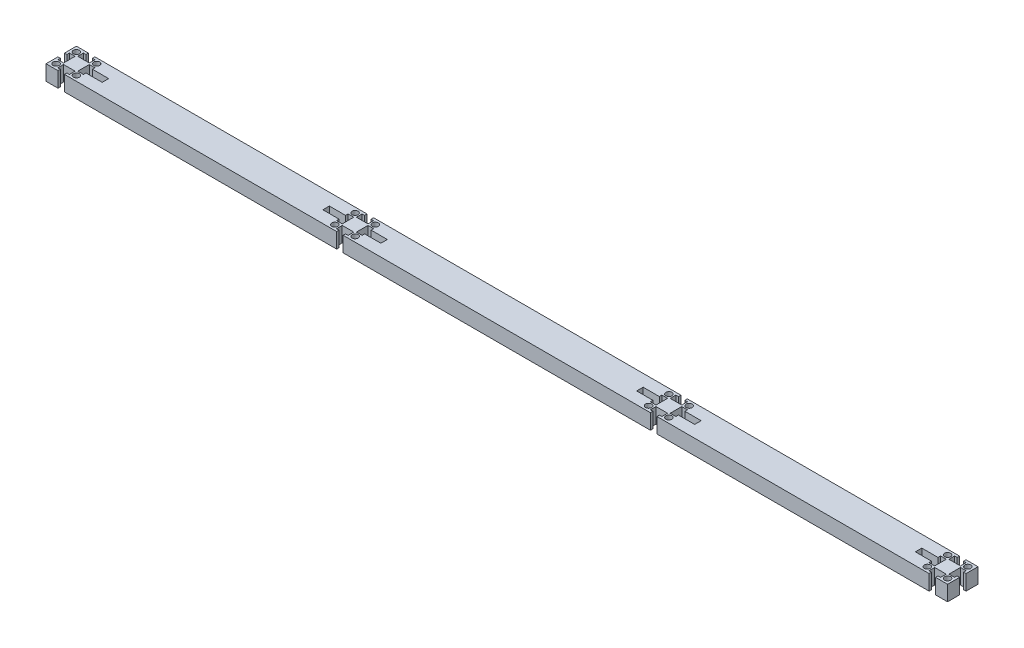
SolidWorks part; units mm, degrees
ref_plane "Front Plane" through (0, 0, 0) normal (0, 0, 1) x (1, 0, 0)
ref_plane "Top Plane" through (0, 0, 0) normal (0, 1, 0) x (1, 0, 0)
ref_plane "Right Plane" through (0, 0, 0) normal (1, 0, 0) x (0, 0, -1)
sketch "Sketch1" plane through (0, 0, 0) normal (0, 1, 0) x (1, 0, 0)
  line L1 (0, 0) -> (152.4, 0)
  line L2 (0, 0) -> (0, 15)
  line L3 (0, 15) -> (152.4, 15)
  line L6 (21.8, 9.1) -> (21.8, 5.9)
  line L7 (5.9, 0) -> (9.1, 0)
  line L8 (0, 5.9) -> (0, 9.1)
  line L9 (4, 4.65) -> (4, 7.5)
  line L10 (4, 7.5) -> (4, 10.35)
  line L11 (4, 10.35) -> (1.2, 10.35)
  line L12 (76.2, 0) -> (76.2, 15)
  line L14 (152.4, 0) -> (292.1, 0)
  line L15 (152.4, 15) -> (292.1, 15)
  line L16 (222.25, 0) -> (222.25, 15)
  line L18 (444.5, 15) -> (292.1, 15)
  line L20 (444.5, 0) -> (292.1, 0)
  line L21 (444.5, 0) -> (444.5, 15)
  line L22 (1.2, 10.35) -> (1.2, 9.1)
  line L23 (1.2, 9.1) -> (0, 9.1)
  line L24 (7.5, 4) -> (4.65, 4)
  line L25 (4.65, 4) -> (4.65, 1.2)
  line L27 (10.35, 1.2) -> (10.35, 4)
  line L28 (10.35, 4) -> (7.5, 4)
  line L29 (4.65, 1.2) -> (5.9, 1.2)
  line L30 (10.35, 1.2) -> (9.1, 1.2)
  line L31 (9.1, 1.2) -> (9.1, 0)
  line L32 (5.9, 1.2) -> (5.9, 0)
  line L33 (1.2, 5.9) -> (0, 5.9)
  line L34 (1.2, 4.65) -> (1.2, 5.9)
  line L35 (1.2, 4.65) -> (4, 4.65)
  line L36 (4.65, 11) -> (7.5, 11)
  line L37 (7.5, 11) -> (10.35, 11)
  line L38 (10.35, 11) -> (10.35, 13.8)
  line L39 (10.35, 13.8) -> (9.1, 13.8)
  line L40 (9.1, 13.8) -> (9.1, 15)
  line L41 (5.9, 13.8) -> (5.9, 15)
  line L42 (4.65, 13.8) -> (5.9, 13.8)
  line L43 (4.65, 13.8) -> (4.65, 11)
  line L44 (11, 10.35) -> (11, 7.5)
  line L45 (11, 7.5) -> (11, 4.65)
  line L46 (11, 4.65) -> (13.8, 4.65)
  line L47 (13.8, 4.65) -> (13.8, 5.9)
  line L48 (13.8, 5.9) -> (21.8, 5.9)
  line L49 (13.8, 9.1) -> (21.8, 9.1)
  line L50 (13.8, 10.35) -> (13.8, 9.1)
  line L51 (13.8, 10.35) -> (11, 10.35)
  line L52 (435.4, 13.8) -> (435.4, 15)
  line L53 (13.8, 5.9) -> (15, 5.9) [skipped]
  line L54 (13.8, 9.1) -> (15, 9.1) [skipped]
  line L55 (434.15, 13.8) -> (435.4, 13.8)
  line L56 (434.15, 11) -> (434.15, 13.8)
  line L57 (437, 11) -> (434.15, 11)
  line L58 (439.85, 11) -> (437, 11)
  line L59 (439.85, 13.8) -> (439.85, 11)
  line L60 (439.85, 13.8) -> (438.6, 13.8)
  line L61 (438.6, 13.8) -> (438.6, 15)
  line L62 (443.3, 4.65) -> (443.3, 5.9)
  line L63 (443.3, 5.9) -> (444.5, 5.9)
  line L64 (443.3, 9.1) -> (444.5, 9.1)
  line L65 (443.3, 10.35) -> (443.3, 9.1)
  line L66 (440.5, 10.35) -> (443.3, 10.35)
  line L67 (440.5, 4.65) -> (440.5, 7.5)
  line L68 (443.3, 4.65) -> (440.5, 4.65)
  line L69 (439.85, 4) -> (439.85, 1.2)
  line L70 (439.85, 1.2) -> (438.6, 1.2)
  line L71 (438.6, 1.2) -> (438.6, 0)
  line L72 (435.4, 1.2) -> (435.4, 0)
  line L73 (434.15, 1.2) -> (435.4, 1.2)
  line L74 (434.15, 1.2) -> (434.15, 4)
  line L75 (434.15, 4) -> (437, 4)
  line L76 (430.7, 5.9) -> (422.7, 5.9)
  line L77 (433.5, 4.65) -> (430.7, 4.65)
  line L78 (433.5, 7.5) -> (433.5, 4.65)
  line L79 (433.5, 10.35) -> (433.5, 7.5)
  line L80 (430.7, 10.35) -> (433.5, 10.35)
  line L81 (430.7, 10.35) -> (430.7, 9.1)
  line L82 (430.7, 9.1) -> (422.7, 9.1)
  line L83 (439.85, 4) -> (437, 4)
  line L84 (440.5, 10.35) -> (440.5, 7.5)
  line L85 (5.9, 15) -> (9.1, 15)
  line L86 (422.7, 9.1) -> (422.7, 5.9)
  line L87 (435.4, 0) -> (438.6, 0)
  line L88 (444.5, 5.9) -> (444.5, 9.1)
  line L89 (435.4, 15) -> (438.6, 15)
  line L90 (430.7, 4.65) -> (430.7, 5.9)
  line L91 (368.3, 15) -> (368.3, 0)
  line L92 (301.2, 1.2) -> (301.2, 0)
  line L93 (302.45, 1.2) -> (301.2, 1.2)
  line L94 (302.45, 1.2) -> (302.45, 4)
  line L95 (302.45, 4) -> (299.6, 4)
  line L96 (296.75, 4) -> (299.6, 4)
  line L97 (296.75, 4) -> (296.75, 1.2)
  line L98 (296.75, 1.2) -> (298, 1.2)
  line L99 (298, 1.2) -> (298, 0)
  line L100 (301.2, 0) -> (298, 0)
  line L101 (303.1, 4.65) -> (305.9, 4.65)
  line L102 (303.1, 7.5) -> (303.1, 4.65)
  line L103 (303.1, 10.35) -> (303.1, 7.5)
  line L104 (305.9, 10.35) -> (303.1, 10.35)
  line L105 (305.9, 10.35) -> (305.9, 9.1)
  line L106 (305.9, 9.1) -> (313.9, 9.1)
  line L107 (313.9, 9.1) -> (313.9, 5.9)
  line L108 (305.9, 5.9) -> (313.9, 5.9)
  line L109 (305.9, 4.65) -> (305.9, 5.9)
  line L110 (301.2, 13.8) -> (301.2, 15)
  line L111 (302.45, 13.8) -> (301.2, 13.8)
  line L112 (302.45, 11) -> (302.45, 13.8)
  line L113 (299.6, 11) -> (302.45, 11)
  line L114 (296.75, 11) -> (299.6, 11)
  line L115 (296.75, 13.8) -> (296.75, 11)
  line L116 (296.75, 13.8) -> (298, 13.8)
  line L117 (298, 13.8) -> (298, 15)
  line L118 (301.2, 15) -> (298, 15)
  line L120 (296.1, 7.5) -> (296.1, 4.65)
  line L121 (296.1, 10.35) -> (296.1, 7.5)
  line L122 (293.3, 10.35) -> (296.1, 10.35)
  line L123 (293.3, 10.35) -> (293.3, 9.1)
  line L124 (293.3, 9.1) -> (285.3, 9.1)
  line L125 (285.3, 9.1) -> (285.3, 5.9)
  line L126 (293.3, 5.9) -> (285.3, 5.9)
  line L127 (293.3, 4.65) -> (293.3, 5.9)
  line L128 (296.1, 4.65) -> (293.3, 4.65)
  line L129 (142.05, 1.2) -> (143.3, 1.2)
  line L130 (142.05, 1.2) -> (142.05, 4)
  line L131 (142.05, 4) -> (144.9, 4)
  line L132 (147.75, 4) -> (144.9, 4)
  line L133 (147.75, 4) -> (147.75, 1.2)
  line L134 (147.75, 1.2) -> (146.5, 1.2)
  line L135 (146.5, 1.2) -> (146.5, 0)
  line L136 (143.3, 0) -> (146.5, 0)
  line L137 (143.3, 1.2) -> (143.3, 0)
  line L138 (141.4, 7.5) -> (141.4, 4.65)
  line L139 (141.4, 10.35) -> (141.4, 7.5)
  line L140 (138.6, 10.35) -> (141.4, 10.35)
  line L141 (138.6, 10.35) -> (138.6, 9.1)
  line L142 (138.6, 9.1) -> (130.6, 9.1)
  line L143 (130.6, 9.1) -> (130.6, 5.9)
  line L144 (138.6, 5.9) -> (130.6, 5.9)
  line L145 (138.6, 4.65) -> (138.6, 5.9)
  line L146 (141.4, 4.65) -> (138.6, 4.65)
  line L147 (142.05, 13.8) -> (143.3, 13.8)
  line L148 (142.05, 11) -> (142.05, 13.8)
  line L149 (144.9, 11) -> (142.05, 11)
  line L150 (147.75, 11) -> (144.9, 11)
  line L151 (147.75, 13.8) -> (147.75, 11)
  line L152 (147.75, 13.8) -> (146.5, 13.8)
  line L153 (146.5, 13.8) -> (146.5, 15)
  line L154 (143.3, 15) -> (146.5, 15)
  line L155 (143.3, 13.8) -> (143.3, 15)
  line L156 (148.4, 10.35) -> (148.4, 7.5)
  line L157 (151.2, 10.35) -> (148.4, 10.35)
  line L158 (151.2, 10.35) -> (151.2, 9.1)
  line L159 (151.2, 9.1) -> (159.2, 9.1)
  line L160 (159.2, 9.1) -> (159.2, 5.9)
  line L161 (151.2, 5.9) -> (159.2, 5.9)
  line L162 (151.2, 4.65) -> (151.2, 5.9)
  line L163 (148.4, 4.65) -> (151.2, 4.65)
  line L164 (148.4, 7.5) -> (148.4, 4.65)
  circle A0 centre (2.5, 2.5) radius 1.5
  circle A1 centre (2.5, 12.5) radius 1.5
  circle A2 centre (12.5, 12.5) radius 1.5
  circle A3 centre (12.5, 2.5) radius 1.5
  circle A4 centre (149.9, 12.5) radius 1.5
  circle A5 centre (139.9, 12.5) radius 1.5
  circle A6 centre (149.9, 2.5) radius 1.5
  circle A7 centre (139.9, 2.5) radius 1.5
  circle A8 centre (432, 12.5) radius 1.5
  circle A9 centre (442, 12.5) radius 1.5
  circle A10 centre (442, 2.5) radius 1.5
  circle A11 centre (432, 2.5) radius 1.5
  circle A12 centre (294.6, 12.5) radius 1.5
  circle A13 centre (304.6, 12.5) radius 1.5
  circle A14 centre (304.6, 2.5) radius 1.5
  circle A15 centre (294.6, 2.5) radius 1.5
  point P89 (7.5, 7.5)
  dimension "D11" = 69.85
  dimension "D1" = 15
  dimension "D2" = 152.4
  dimension "D8" = 4
  dimension "D9" = 8
  dimension "D10" = 8
  dimension "D16" = 1.25
  dimension "D17" = 1.25
extrude "Boss-Extrude1" add sketch "Sketch1" along normal blind 7.5 contours L43 L42 L41 L3 L2 L23 L22 L11 L10 L9 L35 L34 L33 L1 L32 L29 L25 L24 L28 L27 L30 L31 L12 L40 L39 L38 L37 L36 A3 A2 A1 A0 L51 L50 L49 L6 L48 L47 L46 L45 L44 | L147 L155 L3 L12 L1 L137 L129 L130 L131 L132 L133 L134 L135 L14 L16 L15 L153 L152 L151 L150 L149 L148 A6 A4 L164 L156 L157 L158 L159 L160 L161 L162 L163 L138 L146 L145 L144 L143 L142 L141 L140 L139 A5 | L116 L117 L18 L15 L16 L14 L20 L99 L98 L97 L96 L95 L94 L93 L92 L91 L110 L111 L112 L113 L114 L115 A15 A14 A13 A12 L109 L101 L102 L103 L104 L105 L106 L107 L108 L120 L128 L127 L126 L125 L124 L123 L122 | L18 L91 L20 L72 L73 L74 L75 L83 L69 L70 L71 L21 L63 L62 L68 L67 L84 L66 L65 L64 L61 L60 L59 L58 L57 L56 L55 L52 A10 A8 L77 L90 L76 L86 L82 L81 L80 L79 L78 A9 A11 region at (41.7669, 0, -7.5) region at (77.6682, 0, -7.5) region at (223.7182, 0, -7.5) region at (402.7331, 0, -7.5)
